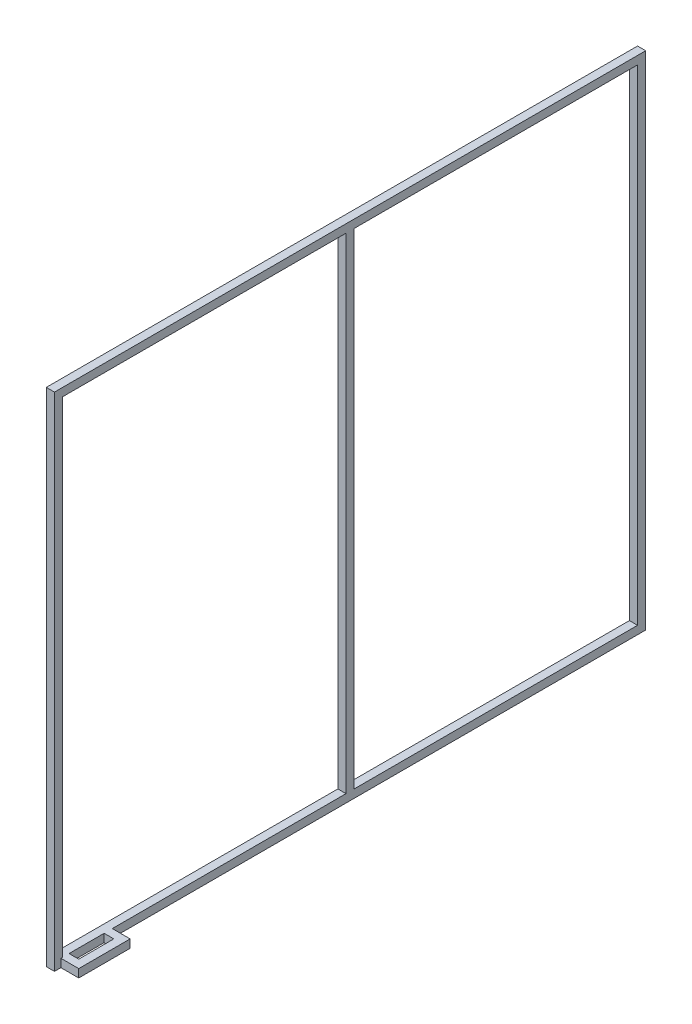
SolidWorks part; units mm, degrees
ref_plane "Front Plane" through (0, 0, 0) normal (0, 0, 1) x (1, 0, 0)
ref_plane "Top Plane" through (0, 0, 0) normal (0, 1, 0) x (1, 0, 0)
ref_plane "Right Plane" through (0, 0, 0) normal (1, 0, 0) x (0, 0, -1)
sketch "Sketch1" plane through (0, 0, 0) normal (1, 0, 0) x (0, 0, -1)
  line L0 (-559.125, -472.0175) -> (-559.125, 472.0175)
  line L2 (-575, -487.8925) -> (-575, 487.8925)
  line L3 (-575, 487.8925) -> (575, 487.8925)
  line L4 (575, -487.8925) -> (575, 487.8925)
  line L5 (-575, -487.8925) -> (575, 487.8925) construction
  line L6 (-575, 487.8925) -> (575, -487.8925) construction
  line L7 (-559.125, 472.0175) -> (559.125, 472.0175)
  line L8 (559.125, -472.0175) -> (559.125, 472.0175)
  line L9 (-575, -487.8925) -> (-559.125, -487.8925)
  line L10 (559.125, -487.8925) -> (575, -487.8925)
  line L11 (-559.125, -487.8925) -> (559.125, -487.8925)
  line L12 (-559.125, -472.0175) -> (559.125, -472.0175)
  line L14 (559.125, -487.8925) -> (559.125, 472.0175) construction
  line L15 (-559.125, -487.8925) -> (-559.125, 472.0175) construction
  point P0 (0, 0)
  point P7 (0, 0)
  dimension "D1" = 1150
  dimension "D2" = 975.785
  dimension "D4" = 15.875
  dimension "D3" = 15.875
extrude "Boss-Extrude1" add sketch "Sketch1" along normal blind 15.875
sketch "Sketch2" plane through (0, -487.8925, 0) normal (0, -1, 0) x (1, 0, 0)
  line L0 (50.625, 469.5) -> (50.625, 555.5) construction
  line L1 (0, 562.5) -> (50.625, 562.5)
  line L2 (0, 562.5) -> (0, 462.5)
  line L3 (0, 462.5) -> (50.625, 462.5)
  line L4 (50.625, 562.5) -> (50.625, 462.5)
  line L5 (73.125, 512.5) -> (47.625, 512.5) construction
  line L6 (15.875, 546.625) -> (34.75, 546.625)
  line L7 (34.75, 546.625) -> (34.75, 478.375)
  line L8 (15.875, 478.375) -> (34.75, 478.375)
  line L9 (15.875, 546.625) -> (15.875, 478.375)
  line L10 (0, 575) -> (0, -575) construction
  point P7 (50.625, 512.5)
  point P17 (25.3125, 462.5)
  dimension "D2" = 100
  dimension "D1" = 15.875
extrude "Boss-Extrude2" add sketch "Sketch2" against normal blind 15.875
sketch "Sketch3" plane through (0, -472.0175, 0) normal (0, 1, 0) x (1, 0, 0)
  line L0 (15.875, 575) -> (15.875, -575) construction
  line L1 (15.875, 7.9375) -> (0, 7.9375)
  line L2 (15.875, 7.9375) -> (15.875, -7.9375)
  line L3 (15.875, -7.9375) -> (0, -7.9375)
  line L4 (0, 7.9375) -> (0, -7.9375)
  line L5 (0, 575) -> (0, -575) construction
  line L6 (195.875, 7.9375) -> (15.875, 7.9375) construction
  line L7 (195.875, -7.9375) -> (15.875, -7.9375) construction
extrude "Boss-Extrude3" add sketch "Sketch3" along normal up to next
